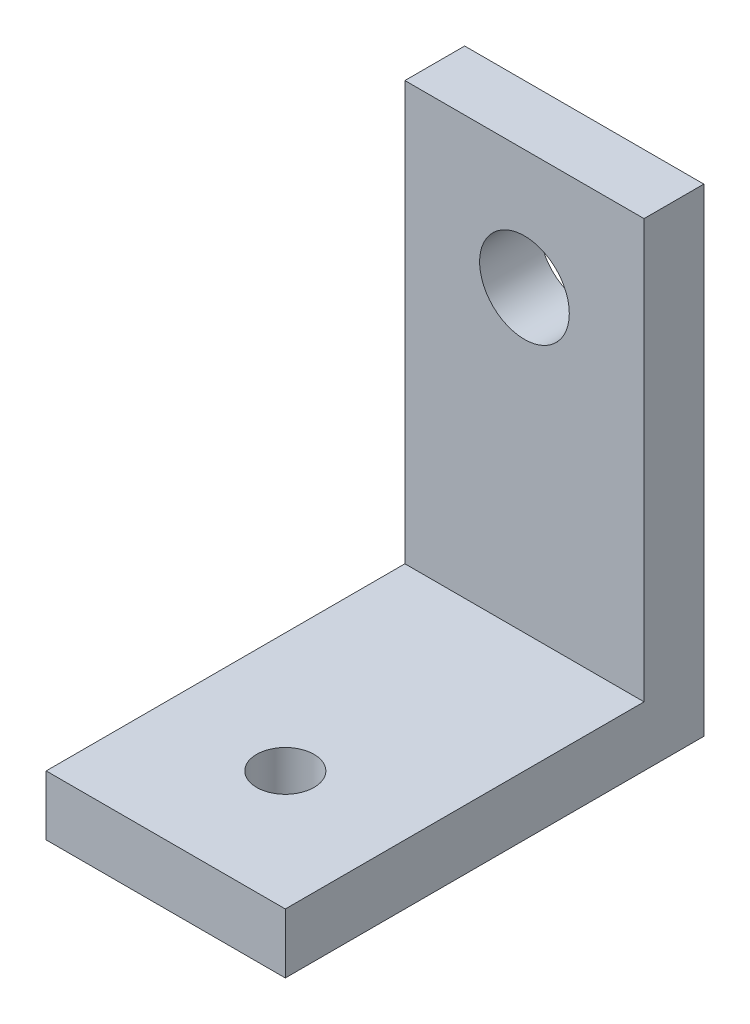
SolidWorks part; units mm, degrees
ref_plane "Front Plane" through (0, 0, 0) normal (0, 0, 1) x (1, 0, 0)
ref_plane "Top Plane" through (0, 0, 0) normal (0, 1, 0) x (1, 0, 0)
ref_plane "Right Plane" through (0, 0, 0) normal (1, 0, 0) x (0, 0, -1)
sketch "Sketch1" plane through (0, 0, 0) normal (0, 0, 1) x (1, 0, 0)
  line L0 (-6.35, 0) -> (-6.35, -19.05)
  line L1 (-6.35, -19.05) -> (6.35, -19.05)
  line L2 (6.35, -19.05) -> (6.35, 0)
  line L5 (-6.35, 0) -> (-6.35, 6.35)
  line L6 (-6.35, 6.35) -> (6.35, 6.35)
  line L7 (6.35, 0) -> (6.35, 6.35)
  circle A1 centre (0, 0) radius 2.3813
  dimension "D1" = 12.7
  dimension "D2" = 4.7625
  dimension "D3" = 25.4
  dimension "D4" = 19.05
extrude "Boss-Extrude1" add sketch "Sketch1" along normal blind 3.175
sketch "Sketch2" plane through (0, 0, 3.175) normal (0, 0, 1) x (1, 0, 0)
  line L0 (6.35, -19.05) -> (6.35, 6.35) construction
  line L1 (-6.35, -19.05) -> (6.35, -19.05)
  line L2 (-6.35, -19.05) -> (-6.35, -15.875)
  line L3 (-6.35, -15.875) -> (6.35, -15.875)
  line L4 (6.35, -19.05) -> (6.35, -15.875)
  dimension "D1" = 3.175
extrude "Boss-Extrude2" add sketch "Sketch2" along normal blind 19.05
sketch "Sketch3" plane through (0, -15.875, 0) normal (0, 1, 0) x (1, 0, 0)
  line L0 (-6.35, -22.225) -> (-6.35, -3.175) construction
  line L1 (6.35, -22.225) -> (-6.35, -22.225) construction
  circle A0 centre (0, -15.875) radius 1.524
  dimension "D1" = 3.048
  dimension "D2" = 6.35
  dimension "D3" = 6.35
extrude "Cut-Extrude1" cut sketch "Sketch3" against normal blind 19.05
